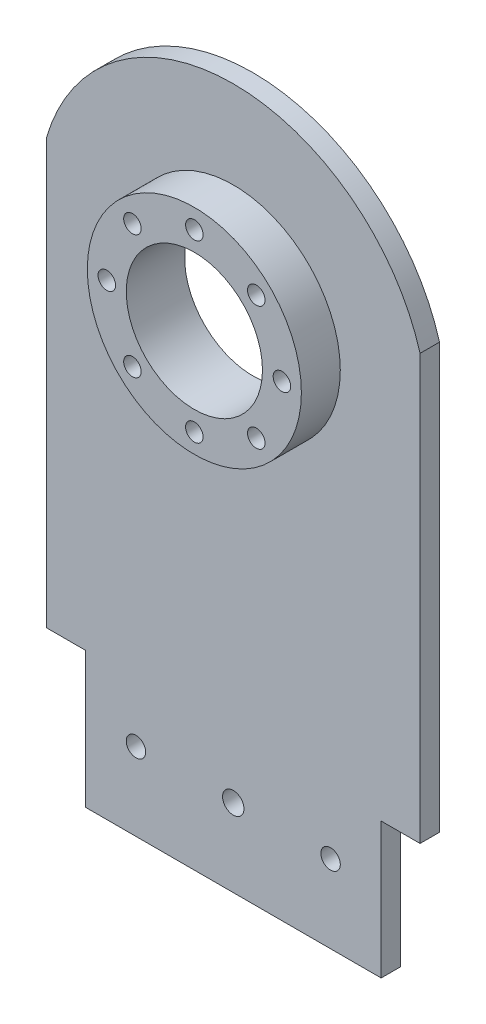
SolidWorks part; units mm, degrees
material "6061 合金"
ref_plane "前视基准面" through (0, 0, 0) normal (0, 0, 1) x (1, 0, 0)
ref_plane "上视基准面" through (0, 0, 0) normal (0, 1, 0) x (1, 0, 0)
ref_plane "右视基准面" through (0, 0, 0) normal (1, 0, 0) x (0, 0, -1)
other "Configuration Table"
sketch "草图1" plane through (0, 0, 0) normal (0, 0, 1) x (1, 0, 0)
  line L0 (0, 0) -> (0, 150.9585) construction
  line L3 (-48, 109.07) -> (-48, 0)
  line L4 (-48, 0) -> (48, 0)
  line L5 (48, 109.07) -> (48, 0)
  circle A0 centre (0, 95.07) radius 17.5
  arc A2 (48, 109.07) -> (-48, 109.07) centre (0, 95.07) ccw
  dimension "D3" = 35
  dimension "D4" = 50
  dimension "D1" = 96
  dimension "D2" = 95.07
extrude "凸台-拉伸1" add sketch "草图1" along normal blind 5
sketch "草图2" plane through (0, 0, 0) normal (0, -1, 0) x (1, 0, 0)
  line L0 (-53.8408, 2.5) -> (58.1589, 2.5) construction
  line L1 (0, 20.308) -> (0, -17.9139) construction
  line L2 (-48, 5) -> (48, 5) construction
  line L3 (-48, 0) -> (48, 0) construction
  circle A0 centre (35, 2.5) radius 2.75
  circle A1 centre (-35, 2.5) radius 2.75
  dimension "D2" = 5.5
  dimension "D1" = 70
extrude "切除-拉伸1" [suppressed] cut sketch "草图2" against normal blind 50
sketch "草图5" plane through (0, 0, 5) normal (0, 0, 1) x (1, 0, 0)
  line L0 (0, 0) -> (0, 169.4961) construction
  line L2 (-58, 0) -> (58, 0)
  line L3 (-58, 0) -> (-58, -50)
  line L4 (-58, -50) -> (58, -50)
  line L5 (58, 0) -> (58, -50)
  dimension "D1" = 116
  dimension "D2" = 50
extrude "碳板突出" [suppressed] add sketch "草图5" against normal up to surface (5 mm away) up to face at (0, 63.535, 0)
sketch "草图6" [suppressed] plane through (0, 0, 5) normal (0, 0, 1) x (1, 0, 0)
  line L0 (0, 0) -> (0, -61.5724) construction
  line L2 (45, -5) -> (50.2, -5)
  line L3 (45, -5) -> (45, -20.2)
  line L4 (45, -20.2) -> (50.2, -20.2)
  line L5 (50.2, -5) -> (50.2, -20.2)
  line L6 (45, -30.2) -> (50.2, -30.2)
  line L7 (45, -30.2) -> (45, -45.4)
  line L8 (45, -45.4) -> (50.2, -45.4)
  line L9 (50.2, -30.2) -> (50.2, -45.4)
  line L10 (-50.2, -30.2) -> (-50.2, -45.4)
  line L11 (-45, -45.4) -> (-50.2, -45.4)
  line L12 (-45, -30.2) -> (-45, -45.4)
  line L13 (-45, -30.2) -> (-50.2, -30.2)
  line L14 (-50.2, -5) -> (-50.2, -20.2)
  line L15 (-45, -20.2) -> (-50.2, -20.2)
  line L16 (-45, -5) -> (-45, -20.2)
  line L17 (-45, -5) -> (-50.2, -5)
  line L18 (58, 0) -> (48, 0) construction
  dimension "D1" = 5.2
  dimension "D2" = 15.2
  dimension "D3" = 15.2
  dimension "D4" = 45
  dimension "D5" = 10
  dimension "D6" = 5
extrude "切除-拉伸4" [suppressed] cut sketch "草图6" against normal through all both
sketch "草图7" [suppressed] plane through (0, 0, 5) normal (0, 0, 1) x (1, 0, 0)
  line L0 (50.2, -20.2) -> (50.2, -5) construction
  line L1 (45, -5) -> (45, -20.2) construction
  line L2 (50.2, -45.4) -> (50.2, -30.2) construction
  line L3 (45, -30.2) -> (45, -45.4) construction
  line L4 (50.2, -5) -> (45, -5) construction
  line L5 (45, -20.2) -> (50.2, -20.2) construction
  line L6 (50.2, -30.2) -> (45, -30.2) construction
  line L7 (45, -45.4) -> (50.2, -45.4) construction
  line L8 (0, 0) -> (0, -72.6402) construction
  circle A0 centre (50.2, -6.55) radius 1.55
  circle A1 centre (50.2, -18.65) radius 1.55
  circle A2 centre (45, -6.55) radius 1.55
  circle A3 centre (45, -18.65) radius 1.55
  circle A4 centre (50.2, -31.75) radius 1.55
  circle A5 centre (45, -31.75) radius 1.55
  circle A6 centre (50.2, -43.85) radius 1.55
  circle A7 centre (45, -43.85) radius 1.55
  circle A8 centre (-45, -43.85) radius 1.55
  circle A9 centre (-50.2, -43.85) radius 1.55
  circle A10 centre (-45, -31.75) radius 1.55
  circle A11 centre (-50.2, -31.75) radius 1.55
  circle A12 centre (-45, -18.65) radius 1.55
  circle A13 centre (-45, -6.55) radius 1.55
  circle A14 centre (-50.2, -18.65) radius 1.55
  circle A15 centre (-50.2, -6.55) radius 1.55
  dimension "D1" = 3.1
extrude "切除-拉伸5" [suppressed] cut sketch "草图7" against normal through all both
sketch "草图8" [suppressed] plane through (0, 0, 5) normal (0, 0, 1) x (1, 0, 0)
  line L0 (0, 22.7135) -> (0, -60.4554) construction
  line L1 (58, -50) -> (58, 0) construction
  line L2 (58, -5) -> (63, -5)
  line L3 (58, -5) -> (58, -20)
  line L4 (58, -20) -> (63, -20)
  line L5 (63, -5) -> (63, -20)
  line L6 (58, 0) -> (48, 0) construction
  line L7 (58, -30) -> (63, -30)
  line L8 (58, -30) -> (58, -45)
  line L9 (58, -45) -> (63, -45)
  line L10 (63, -30) -> (63, -45)
  line L11 (-63, -30) -> (-63, -45)
  line L12 (-58, -45) -> (-63, -45)
  line L13 (-58, -30) -> (-58, -45)
  line L14 (-58, -30) -> (-63, -30)
  line L15 (-63, -5) -> (-63, -20)
  line L16 (-58, -20) -> (-63, -20)
  line L17 (-58, -5) -> (-58, -20)
  line L18 (-58, -5) -> (-63, -5)
  dimension "D1" = 5
  dimension "D2" = 15
  dimension "D3" = 5
  dimension "D4" = 10
  dimension "D5" = 15
extrude "碳板榫卯突起" [suppressed] add sketch "草图8" against normal up to surface (5 mm away) up to face at (0, 63.535, 0)
sketch "草图9" [suppressed] plane through (0, 0, 5) normal (0, 0, 1) x (1, 0, 0)
  line L0 (58, -5) -> (58, 0) construction
  line L1 (58, -30) -> (58, -20) construction
  line L2 (58, -50) -> (58, -45) construction
  line L3 (63, -5) -> (58, -5) construction
  line L4 (58, -20) -> (63, -20) construction
  line L5 (63, -30) -> (58, -30) construction
  line L6 (58, -45) -> (63, -45) construction
  line L7 (0, 0) -> (0, -84.76) construction
  circle A0 centre (58, -3.45) radius 1.55
  circle A1 centre (58, -21.55) radius 1.55
  circle A2 centre (58, -28.45) radius 1.55
  circle A3 centre (58, -46.55) radius 1.55
  circle A4 centre (-58, -46.55) radius 1.55
  circle A5 centre (-58, -28.45) radius 1.55
  circle A6 centre (-58, -21.55) radius 1.55
  circle A7 centre (-58, -3.45) radius 1.55
  dimension "D1" = 3.1
extrude "碳板榫卯半圆" [suppressed] cut sketch "草图9" against normal up to surface (5 mm away) up to face at (0, 63.535, 0)
fillet "碳板榫卯圆角" [suppressed] radius 5
sketch "草图10" plane through (0, 0, 5) normal (0, 0, 1) x (1, 0, 0)
  line L0 (0, 87.232) -> (0, -56.3055) construction
  line L1 (-48, 0) -> (48, 0) construction
  line L2 (-38, 0) -> (38, 0)
  line L3 (-38, 0) -> (-38, -34.93)
  line L4 (-38, -34.93) -> (38, -34.93)
  line L5 (38, 0) -> (38, -34.93)
  circle A0 centre (25, -14.93) radius 2.5
  circle A1 centre (-25, -14.93) radius 2.5
  circle A2 centre (0, -14.93) radius 2.75
  dimension "D3" = 5
  dimension "D6" = 5.5
  dimension "D1" = 76
  dimension "D2" = 34.93
  dimension "D4" = 20
  dimension "D5" = 50
extrude "凸台-拉伸2" add sketch "草图10" against normal up to surface (5 mm away) up to face at (0, 63.535, 0)
sketch "草图11" plane through (0, 0, 5) normal (0, 0, 1) x (1, 0, 0)
  circle A0 centre (0, 95.07) radius 27.5
  circle A1 centre (0, 95.07) radius 17.5 construction
  circle A2 centre (0, 95.07) radius 17.5
  dimension "D1" = 55
extrude "凸台-拉伸3" add sketch "草图11" along normal blind 10
sketch "草图12" plane through (0, 0, 15) normal (0, 0, 1) x (1, 0, 0)
  circle A0 centre (0, 95.07) radius 22.5 construction
  circle A1 centre (0, 117.57) radius 2.25
  circle A2 centre (15.9099, 110.9799) radius 2.25
  circle A3 centre (22.5, 95.07) radius 2.25
  circle A4 centre (15.9099, 79.1601) radius 2.25
  circle A5 centre (0, 72.57) radius 2.25
  circle A6 centre (-15.9099, 79.1601) radius 2.25
  circle A7 centre (-22.5, 95.07) radius 2.25
  circle A8 centre (-15.9099, 110.9799) radius 2.25
  point P21 (0, 95.07)
  dimension "D1" = 45
  dimension "D2" = 4.5
  dimension "D3" = 8
extrude "切除-拉伸6" cut sketch "草图12" against normal blind 40
sketch "草图13" plane through (0, 0, 5) normal (0, 0, 1) x (1, 0, 0)
  line L0 (38, -34.93) -> (38, 0) construction
  line L1 (28, -15) -> (38, -15)
  line L2 (28, -15) -> (28, -35)
  line L3 (28, -35) -> (38, -35)
  line L4 (38, -15) -> (38, -35)
  line L5 (38, 0) -> (48, 0) construction
  line L6 (0, 0) -> (0, -37.583) construction
  line L7 (-38, -15) -> (-38, -35)
  line L8 (-28, -35) -> (-38, -35)
  line L9 (-28, -15) -> (-28, -35)
  line L10 (-28, -15) -> (-38, -15)
  circle A0 centre (33, -10) radius 2.75
  circle A1 centre (23, -25) radius 2.75
  circle A2 centre (33, -40) radius 2.75
  circle A3 centre (-33, -40) radius 2.75
  circle A4 centre (-23, -25) radius 2.75
  circle A5 centre (-33, -10) radius 2.75
  dimension "D10" = 5.5
  dimension "D1" = 10
  dimension "D2" = 20
  dimension "D3" = 5
  dimension "D4" = 5
  dimension "D5" = 5
  dimension "D6" = 10
  dimension "D7" = 5
  dimension "D8" = 5
  dimension "D9" = 15
extrude "切除-拉伸7" [suppressed] cut sketch "草图13" against normal blind 10
fillet "圆角1" [suppressed] radius 2
